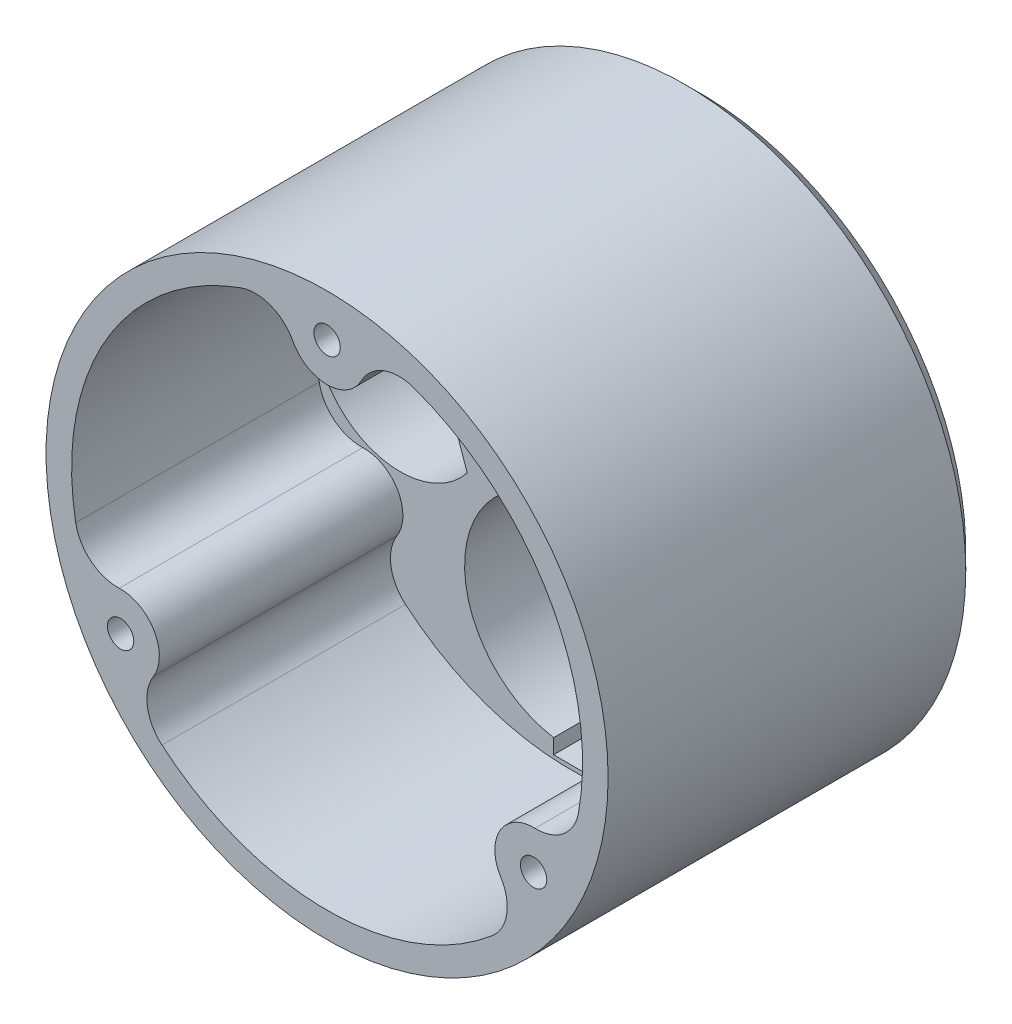
SolidWorks part; units mm, degrees
ref_plane "Front" through (0, 0, 0) normal (0, 0, 1) x (1, 0, 0)
ref_plane "Top" through (0, 0, 0) normal (0, 1, 0) x (1, 0, 0)
ref_plane "Right" through (0, 0, 0) normal (1, 0, 0) x (0, 0, -1)
sketch "Sketch1" plane through (0, 0, 0) normal (0, 0, 1) x (1, 0, 0)
  line L0 (-11.5, 19.9186) -> (0, 0) construction
  line L5 (0, 0) -> (11.5, 19.9186) construction
  line L6 (0, 0) -> (35.9974, 0) construction
  circle A1 centre (0, 0) radius 12.45
  circle A2 centre (0, 0) radius 15.45
  circle A3 centre (11.5, 19.9186) radius 1.05
  circle A4 centre (-11.5, 19.9186) radius 1.05
  circle A5 centre (-11.5, 19.9186) radius 4.05
  circle A6 centre (11.5, 19.9186) radius 4.05
  circle A7 centre (0, 15.45) radius 30
  circle A8 centre (-11.5, 19.9186) radius 12.5 construction
  circle A9 centre (11.5, 19.9186) radius 5 construction
  circle A10 centre (0, 15.45) radius 33
  point P2 (0, 0)
  point P16 (0, 15.45)
  dimension "D1" = 24.9
  dimension "D2" = 3
  dimension "D7" = 2.1
  dimension "D8" = 2.1
  dimension "D9" = 3
  dimension "D10" = 3
  dimension "D11" = 10
  dimension "D12" = 25
  dimension "D13" = 60
  dimension "D14" = 3
  dimension "D3" = 60
  dimension "D4" = 60
  dimension "D5" = 23
  dimension "D6" = 23
extrude "Boss-Extrude2" add sketch "Sketch1" along normal blind 12.4 contours A10 A7 A2 | A6 A3 | A5 A4 | A7 A2 | A2 A7 A1 region at (12.8555, -7.7664, 0) region at (0, -14.7357, 0) region at (-15.4354, 19.9186, 0) region at (7.5646, 19.9186, 0) region at (-32.0666, 15.45, 0)
sketch "Sketch2" plane through (0, 0, 0) normal (0, 0, -1) x (-1, 0, 0)
  circle A0 centre (0, 15.45) radius 33
  arc A1 (7.1877, -13.6762) -> (-7.1877, -13.6762) centre (0, 0) ccw construction
extrude "Boss-Extrude3" add sketch "Sketch2" along normal blind 3
sketch "Sketch3" plane through (0, 0, 12.4) normal (0, 0, 1) x (1, 0, 0)
  circle A0 centre (0, 15.45) radius 33
  circle A2 centre (0, 15.45) radius 33 construction
  circle A3 centre (0, 15.45) radius 30
extrude "Boss-Extrude4" add sketch "Sketch3" along normal blind 28.6
fillet "Fillet1" radius 10 2 edges at (7.1877, -13.6762, 6.2) (-7.1877, -13.6762, 6.2)
sketch "Sketch4" plane through (0, 0, 0) normal (0, 0, 1) x (1, 0, 0)
  line L0 (-15.356, 18.68) -> (-12.1402, 9.5561)
  line L1 (12.1402, 9.5561) -> (15.356, 18.68)
  line L2 (8.1604, 22.2098) -> (0, 15.45)
  line L3 (-8.1604, 22.2098) -> (0, 15.45)
  line L4 (-8.1604, 22.2098) -> (-10.091, 17.8303)
  line L5 (-10.091, 17.8303) -> (-15.356, 18.68)
  line L6 (8.1604, 22.2098) -> (9.704, 17.8303)
  line L7 (9.704, 17.8303) -> (15.356, 18.68)
  line L8 (-12.1402, 9.5561) -> (-4.4574, 12.839)
  line L9 (-4.4574, 12.839) -> (4.0802, 12.839)
  line L10 (4.0802, 12.839) -> (12.1402, 9.5561)
  arc A0 (12.1402, 9.5561) -> (-12.1402, 9.5561) centre (0, 0) ccw construction
  circle A1 centre (-11.5, 19.9186) radius 4.05 construction
  circle A2 centre (11.5, 19.9186) radius 4.05 construction
extrude "Boss-Extrude5" add sketch "Sketch4" along normal blind 12.4
chamfer "Chamfer1" distance 4 angle 45 3 edges at (23.3394, 6.3161, 0) (-23.3394, 6.3161, 0) (0, 45.45, 0)
fillet "Fillet2" radius 5 2 edges at (-13.385, 23.5032, 0) (13.385, 23.5032, 0)
sketch "Sketch5" plane through (0, 0, 12.4) normal (0, 0, 1) x (1, 0, 0)
  line L0 (0, 15.45) -> (-25.9808, 0.45) construction
  line L1 (0, 15.45) -> (25.9808, 0.45) construction
  line L2 (0, 15.45) -> (0, 45.45) construction
  circle A0 centre (0, 15.45) radius 30 construction
  arc A1 (29.9968, 15.8869) -> (-29.9968, 15.8869) centre (0, 15.45) ccw construction
  circle A2 centre (0, 43.45) radius 4.55
  circle A3 centre (0, 43.45) radius 1.55
  circle A4 centre (24.2487, 1.45) radius 4.55
  circle A5 centre (24.2487, 1.45) radius 1.55
  circle A6 centre (-24.2487, 1.45) radius 4.55
  circle A7 centre (-24.2487, 1.45) radius 1.55
  point P22 (0, 15.45)
  dimension "D3" = 3.1
  dimension "D4" = 3
  dimension "D1" = 120
  dimension "D2" = 120
  dimension "D5" = 28
  dimension "D6" = 3
extrude "Boss-Extrude6" add sketch "Sketch5" along normal up to surface (28.6 mm away) and the other way blind 14.4 up to face at (33, 15.45, 41)
fillet "Fillet3" radius 5 6 edges at (23.6126, -3.0553, 26.7) (27.8324, 4.2536, 26.7) (-23.6126, -3.0553, 26.7) (-27.8324, 4.2536, 26.7) (4.2198, 45.1517, 22.5) (-4.2198, 45.1517, 22.5)
chamfer "Chamfer2" distance 2 angle 45 1 edges at (-33, 15.45, -3)
sketch "Sketch6" plane through (0, 0, 12.4) normal (0, 0, 1) x (1, 0, 0)
  line L1 (-2, -12.0349) -> (2, -12.0349)
  line L2 (-2, -12.0349) -> (-2, -14.0349)
  line L3 (-2, -14.0349) -> (2, -14.0349)
  line L4 (2, -12.0349) -> (2, -14.0349)
  point P5 (1.0684, -12.0349)
  dimension "D1" = 2
extrude "Cut-Extrude1" cut sketch "Sketch6" against normal blind 23.4
